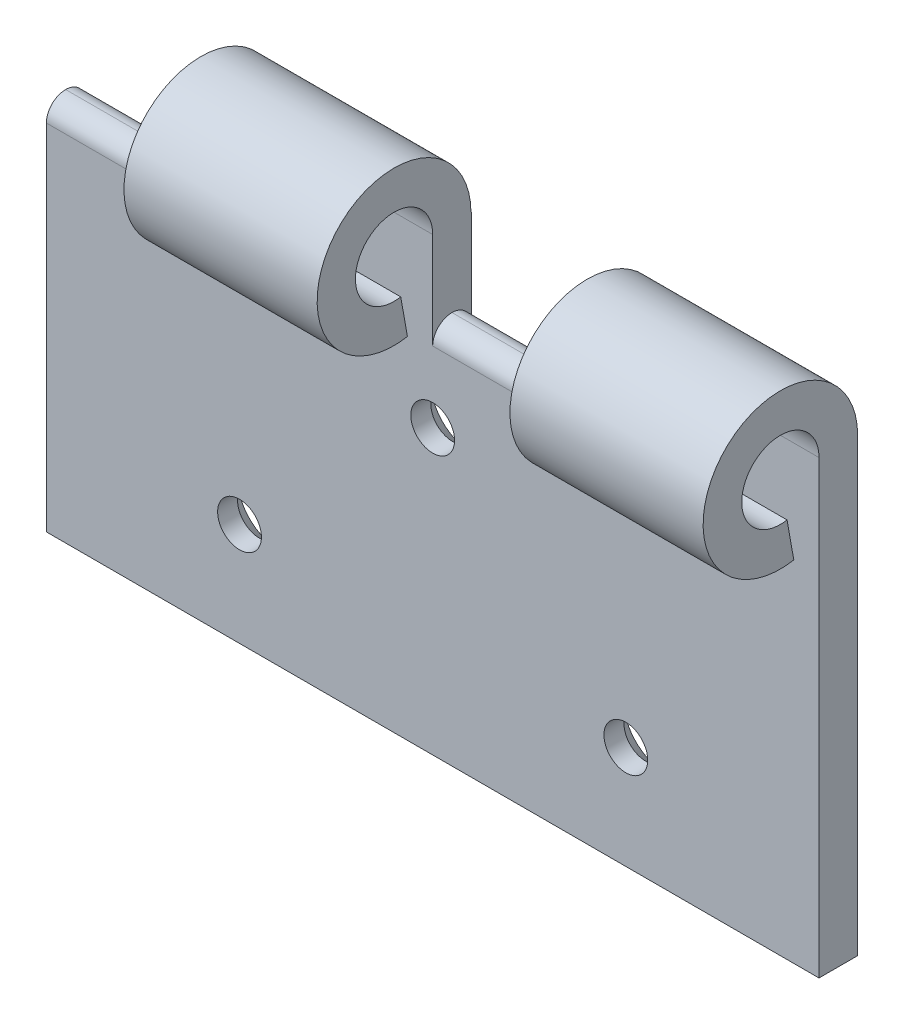
SolidWorks part; units mm, degrees
ref_plane "Front Plane" through (0, 0, 0) normal (0, 0, 1) x (1, 0, 0)
ref_plane "Top Plane" through (0, 0, 0) normal (0, 1, 0) x (1, 0, 0)
ref_plane "Right Plane" through (0, 0, 0) normal (1, 0, 0) x (0, 0, -1)
sketch "Sketch1" plane through (0, 0, 0) normal (0, 0, 1) x (1, 0, 0)
  line L1 (-30, -17.5) -> (30, -17.5)
  line L2 (-30, -17.5) -> (-30, 17.5)
  line L3 (-30, 17.5) -> (30, 17.5)
  line L4 (30, -17.5) -> (30, 17.5)
  line L5 (-30, -17.5) -> (30, 17.5) construction
  line L6 (-30, 17.5) -> (30, -17.5) construction
  point P0 (0, 0)
  dimension "D2" = 35
  dimension "D3" = 60
extrude "Boss-Extrude1" add sketch "Sketch1" along normal blind 3 contours L1 L4 L3 L2 region at (0, 0, 0)
sketch "Sketch2" plane through (0, 0, 0) normal (0, 0, 1) x (1, 0, 0)
  point P0 (0, 4.5)
  point P2 (-15, -9.5)
  point P4 (15, -9.5)
  point P12 (19.5688, -4.371)
  point P13 (0, 0)
  dimension "D1" = 4.5
  dimension "D2" = 9.5
  dimension "D3" = 9.5
  dimension "D4" = 15
  dimension "D5" = 15
hole_wizard "CSK for M3 Countersunk Flat Head Screw1" positions "Sketch2" profile "Sketch3" countersink size "M3" standard "ISO"
sketch "Sketch3" plane through (0, 4.5, 0) normal (1, 0, 0) x (0, 1, 0)
  line L0 (0, 0) -> (0, 4.0215)
  line L1 (0, 4.0215) -> (1.7, 3)
  line L2 (1.7, 3) -> (1.7, 1.45)
  line L3 (1.7, 1.45) -> (3.15, 0)
  line L5 (3.15, 0) -> (0, 0)
  line L6 (-1.7, 1.45) -> (-3.15, 0) construction
  line L10 (0, 4.0215) -> (-1.7, 3) construction
  line L11 (0, -6.35) -> (0, 107.95) construction
  dimension "Hole Dia." = 3.4
  dimension "Hole Depth" = 3
  dimension "Near C'Sink Dia." = 6.3
  dimension "Near C'Sink Angle" = 90
  dimension "Drill Angle" = 118
sketch "Sketch5" plane through (30, 0, 0) normal (1, 0, 0) x (0, 0, -1)
  line L0 (0, 17.5) -> (-6, 17.5) construction
  line L1 (0, -17.5) -> (0, 17.5) construction
  line L2 (-6, 17.5) -> (-5.4791, 14.5456) construction
  line L5 (-3, -17.5) -> (-3, 17.5) construction
  line L6 (-5.4791, 14.5456) -> (-4.9581, 11.5912)
  line L7 (-3, 17.5) -> (-3, 12.3038)
  arc A0 (-3, 12.3038) -> (-4.9581, 11.5912) centre (-6, 17.5) ccw
  arc A1 (-3, 17.5) -> (-5.4791, 14.5456) centre (-6, 17.5) ccw
  circle A2 centre (-6, 17.5) radius 3 construction
  circle A3 centre (-6, 17.5) radius 6 construction
  point P4 (0, 0)
  point P14 (0, 0)
  dimension "D1" = 6
  dimension "D3" = 80
  dimension "D2" = 3
extrude "Boss-Extrude2" add sketch "Sketch5" against normal blind 15
sketch "Sketch6" plane through (0, 0, 0) normal (-1, 0, 0) x (0, 0, 1)
  line L0 (3, 17.5) -> (3, 12.3353)
  line L1 (3, -17.5) -> (3, 17.5) construction
  line L3 (5.4791, 14.5456) -> (4.9581, 11.5912)
  arc A2 (4.9628, 11.6179) -> (3, 12.3353) centre (6, 17.5) ccw
  arc A3 (5.4791, 14.5456) -> (3, 17.5) centre (6, 17.5) ccw
  dimension "D1" = 11.9456
extrude "Boss-Extrude3" add sketch "Sketch6" along normal blind 15 contours L3 A3 L0 A2 | A2 L0 A3 L3 region at (0, 14.9176, 2.8311)
sketch "Sketch8" plane through (0, 0, 0) normal (1, 0, 0) x (0, 0, -1)
  line L6 (0, 17.5) -> (0, -17.5) construction
  line L7 (-3, 17.5) -> (0, 17.5)
  line L8 (-3, 17.5) -> (-3, 11.5)
  line L9 (-3, 11.5) -> (0, 11.5)
  line L10 (0, 17.5) -> (0, 11.5)
  dimension "D1" = 6
sketch "Sketch9" plane through (-15, 0, 0) normal (-1, 0, 0) x (0, 0, 1)
  line L3 (0, 17.5) -> (0.0048, 17.5)
  line L10 (0.0048, 17.5) -> (0, 17.5)
  line L15 (0, 17.5) -> (3, 17.5)
  line L16 (0, 17.5) -> (0, 11.5)
  line L17 (0, 11.5) -> (3, 11.5)
  line L18 (3, 17.5) -> (3, 11.5)
  line M3 (0.0272, 17.5) -> (3, 17.5)
extrude "Cut-Extrude4" cut sketch "Sketch9" along normal blind 15 contours L18 L15 L3 L16 L17 M3 region at (-15, 14.5, 1.5)
extrude "Cut-Extrude5" cut sketch "Sketch8" along normal blind 15
fillet "Fillet4" radius 1.5 4 edges at (-22.5, 11.5, 0) (-22.5, 11.5, 3) (7.5, 11.5, 0) (7.5, 11.5, 3)
